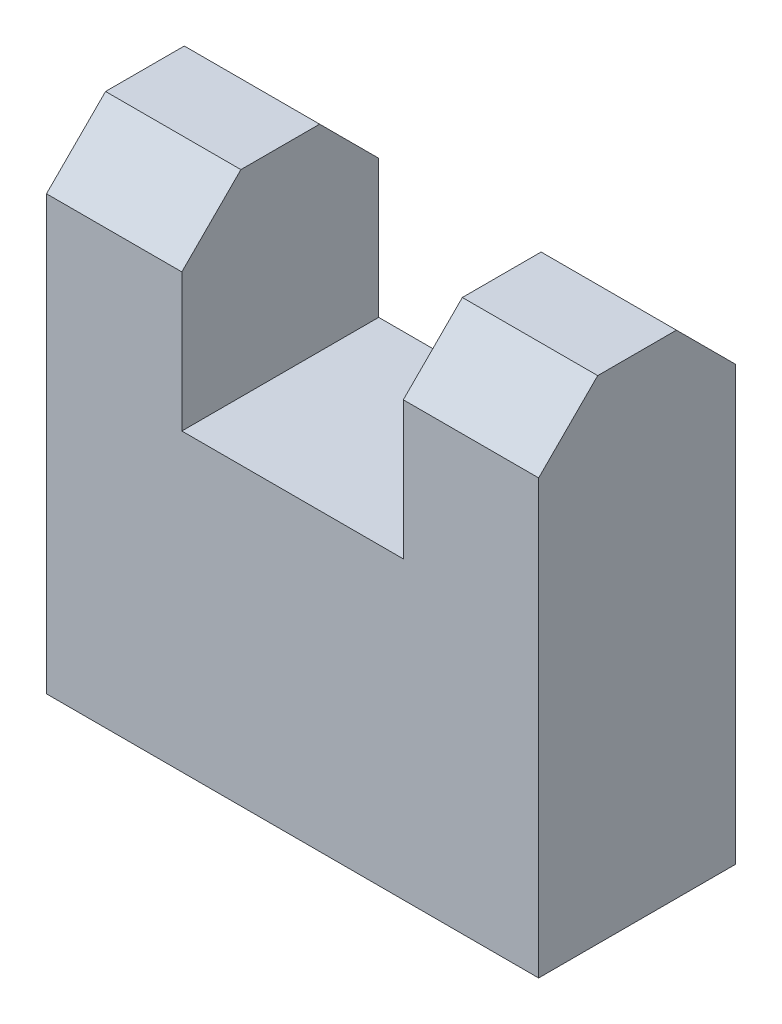
SolidWorks part; units mm, degrees
ref_plane "Ebene vorne" through (0, 0, 0) normal (0, 0, 1) x (1, 0, 0)
ref_plane "Ebene oben" through (0, 0, 0) normal (0, 1, 0) x (1, 0, 0)
ref_plane "Ebene rechts" through (0, 0, 0) normal (1, 0, 0) x (0, 0, -1)
sketch "Skizze1" plane through (0, 0, 0) normal (0, 0, 1) x (1, 0, 0)
  line L0 (50, 0) -> (-50, 0)
  line L1 (-50, 0) -> (-50, 100)
  line L2 (-50, 100) -> (-22.5, 100)
  line L3 (-22.5, 100) -> (-22.5, 60)
  line L4 (-22.5, 60) -> (22.5, 60)
  line L6 (0, 60) -> (0, 0) construction
  line L7 (22.5, 100) -> (22.5, 60)
  line L8 (50, 100) -> (22.5, 100)
  line L9 (50, 0) -> (50, 100)
  dimension "D1" = 100
  dimension "D2" = 100
  dimension "D3" = 40
  dimension "D4" = 45
extrude "Aufsatz-Linear austragen1" add sketch "Skizze1" along normal blind 40
chamfer "Fase1" distance 12 angle 45 4 edges at (-36.25, 100, 0) (36.25, 100, 0) (36.25, 100, 40) (-36.25, 100, 40)
